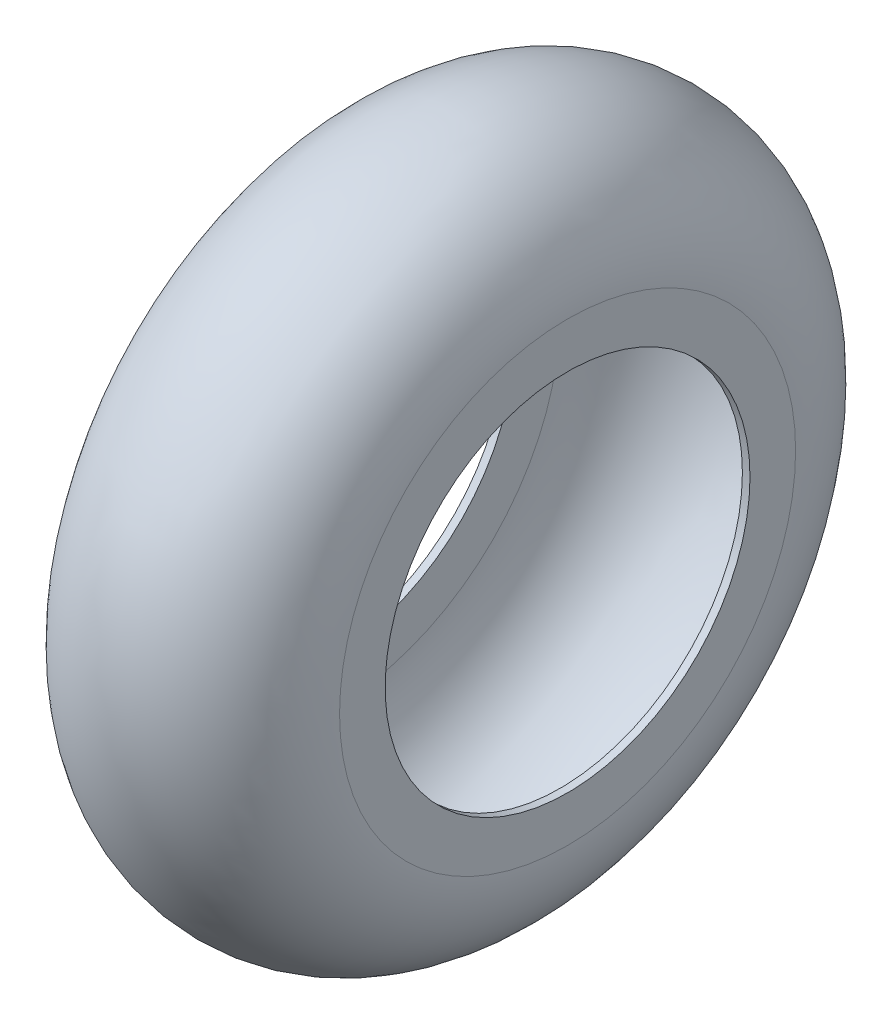
SolidWorks part; units mm, degrees
material "Natural Rubber"
ref_plane "Front Plane" through (0, 0, 0) normal (0, 0, 1) x (1, 0, 0)
ref_plane "Top Plane" through (0, 0, 0) normal (0, 1, 0) x (1, 0, 0)
ref_plane "Right Plane" through (0, 0, 0) normal (1, 0, 0) x (0, 0, -1)
sketch "Sketch2" plane through (0, 0, 0) normal (1, 0, 0) x (0, 0, -1)
  circle A0 centre (0, 0) radius 292.1
  circle A1 centre (0, 0) radius 152.4
  dimension "D1" = 584.2
  dimension "D2" = 304.8
extrude "Boss-Extrude1" add sketch "Sketch2" against normal blind 203.2
fillet "Fillet1" 2 edges at (-203.2, 0, -292.1) (0, 0, -292.1) type full round first side face at (-203.2, 0, -152.4) second side face at (0, 0, -152.4) middle face at (-203.2, 0, -292.1)
sketch "Sketch3" plane through (0, 0, 0) normal (0, 0, 1) x (1, 0, 0)
  line L0 (-101.6, 292.1) -> (-101.6, -292.1) construction
  arc A0 (0, 190.5) -> (-203.2, 190.5) centre (-101.6, 190.5) ccw construction
  arc A1 (-203.2, -190.5) -> (0, -190.5) centre (-101.6, -190.5) ccw construction
  point P8 (-83.5506, 0)
shell "Shell1" thickness 6.35 removed face at (-203.2, 0, -152.4)
